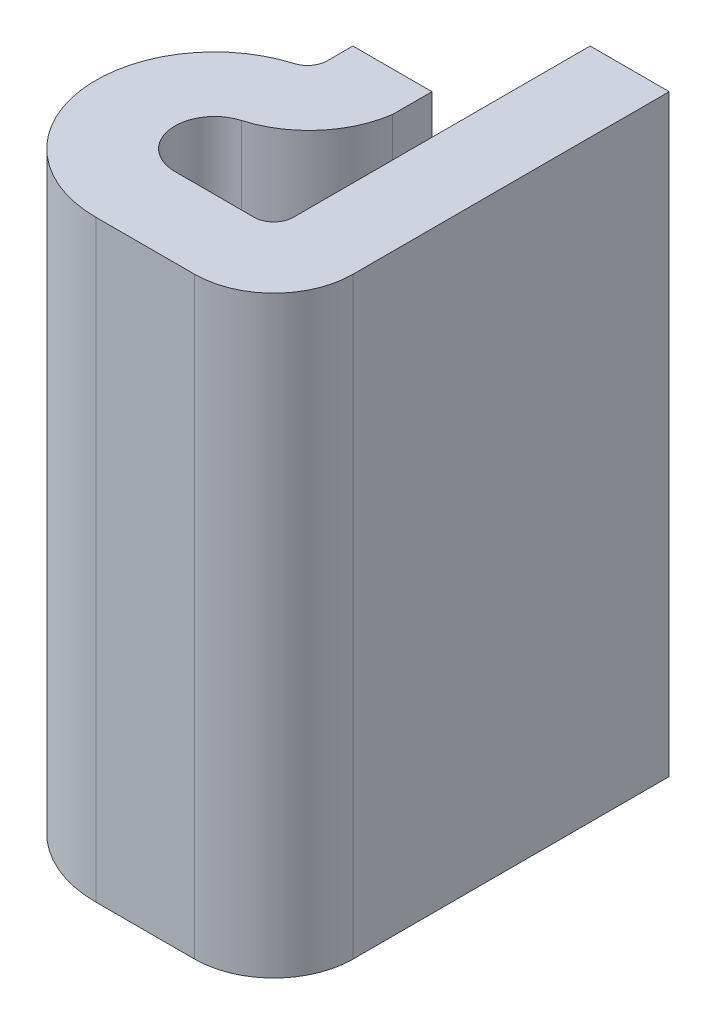
SolidWorks part; units mm, degrees
ref_plane "Front Plane" through (0, 0, 0) normal (0, 0, 1) x (1, 0, 0)
ref_plane "Top Plane" through (0, 0, 0) normal (0, 1, 0) x (1, 0, 0)
ref_plane "Right Plane" through (0, 0, 0) normal (1, 0, 0) x (0, 0, -1)
sketch "Sketch1" plane through (0, 16.5, 0) normal (0, -1, 0) x (1, 0, 0)
  line L0 (33.25, 39.5) -> (33.25, 2) construction
  line L1 (30.75, 41.5) -> (30.75, 34.5) construction
  line L2 (33.25, 39.5) -> (33.25, 2) construction
  line L3 (32.25, 34.5) -> (32.25, 35.5)
  line L4 (1.75, 39.5) -> (31.25, 39.5) construction
  line L5 (30.75, 39.5) -> (33.25, 39.5) construction
  line L6 (33.25, 39) -> (33.25, 31.5)
  line L7 (33.25, 31.5) -> (35.25, 31.5)
  line L8 (35.25, 31.5) -> (35.25, 39.5)
  line L9 (33.25, 41.5) -> (30.75, 41.5)
  line L11 (30.75, 39.5) -> (32.75, 39.5)
  line L12 (30.25, 34.5) -> (32.25, 34.5)
  line L13 (30.25, 34.5) -> (30.25, 35.1459)
  arc A0 (30.75, 41.5) -> (29.8929, 35.6251) centre (30.75, 38.5) ccw
  arc A1 (30.4718, 37.5395) -> (32.25, 35.5) centre (29.7763, 35.1382) cw
  arc A3 (30.4718, 37.5395) -> (30.75, 39.5) centre (30.75, 38.5) cw
  arc A4 (35.25, 39.5) -> (33.25, 41.5) centre (33.25, 39.5) ccw
  arc A5 (33.25, 39) -> (32.75, 39.5) centre (32.75, 39) ccw
  arc A6 (30.25, 35.1459) -> (29.8929, 35.6251) centre (29.75, 35.1459) ccw
  point P26 (30.25, 35.542)
  point P29 (32.25, 35.5)
  dimension "D6" = 1
  dimension "D7" = 1
  dimension "D8" = 3
  dimension "D4" = 2.5
  dimension "D5" = 2
  dimension "D9" = 2
  dimension "D11" = 0.5
  dimension "D3" = 1
  dimension "D13" = 0.5
  dimension "D1" = 2
  dimension "D2" = 2
  dimension "D10" = 8
  dimension "D12" = 2.5
extrude "Boss-Extrude1" add sketch "Sketch1" along normal blind 7.5 and the other way blind 7.5
